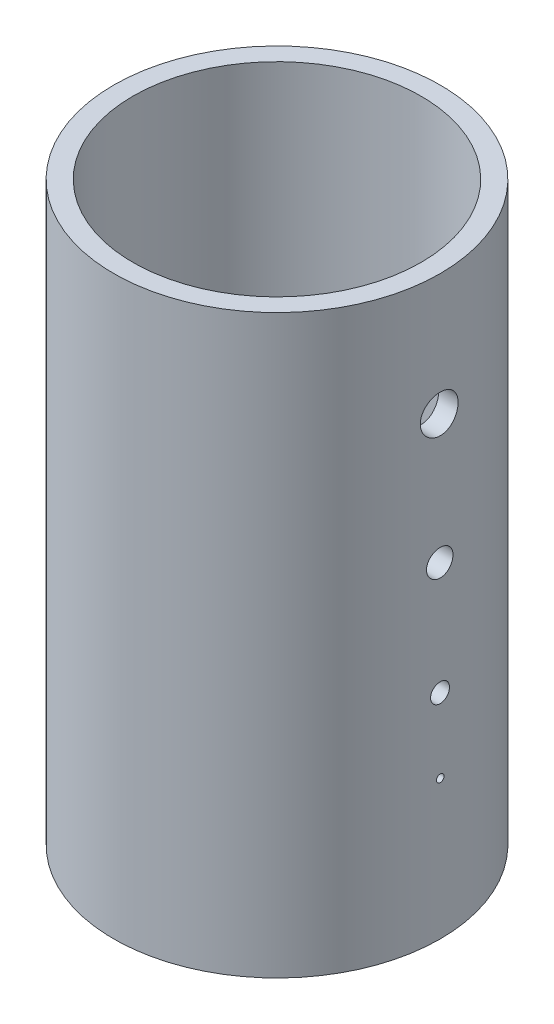
SolidWorks part; units mm, degrees
ref_plane "Front Plane" through (0, 0, 0) normal (0, 0, 1) x (1, 0, 0)
ref_plane "Top Plane" through (0, 0, 0) normal (0, 1, 0) x (1, 0, 0)
ref_plane "Right Plane" through (0, 0, 0) normal (1, 0, 0) x (0, 0, -1)
sketch "Sketch1" plane through (0, 0, 0) normal (0, 0, 1) x (1, 0, 0)
  line L0 (0, 0) -> (-43.18, 0)
  line L1 (-43.18, 0) -> (-43.18, 152.4)
  line L3 (-38.1, 152.4) -> (-38.1, 34.925)
  line L4 (-12.7, 9.525) -> (0, 9.525)
  line L5 (0, 9.525) -> (0, 0)
  line L11 (-43.18, 152.4) -> (-38.1, 152.4)
  arc A0 (-38.1, 34.925) -> (-12.7, 9.525) centre (-12.7, 34.925) ccw
  point P9 (-38.1, 9.525)
  dimension "D3" = 25.4
  dimension "D1" = 38.1
  dimension "D2" = 152.4
  dimension "D4" = 5.08
  dimension "D5" = 9.525
revolve "Revolve1" add sketch "Sketch1" angle 360 about L5
sketch "Sketch2" [suppressed] plane through (0, 0, 0) normal (0, -1, 0) x (1, 0, 0)
  circle A0 centre (0, 0) radius 12.7 construction
  circle A1 centre (0, 12.7) radius 2.032
  point P3 (0, 12.7)
  point P7 (8.9803, 8.9803)
  point P8 (12.7, 0)
  point P9 (8.9803, -8.9803)
  point P10 (0, -12.7)
  point P11 (-8.9803, -8.9803)
  point P12 (-12.7, 0)
  point P13 (-8.9803, 8.9803)
  point P14 (0, 0)
  dimension "D1" = 25.4
  dimension "D3" = 4.064
  dimension "D2" = 8
extrude "Cut-Extrude1" [suppressed] cut sketch "Sketch2" against normal up to next draft 4.35 contours A1
pattern_circular "CirPattern1" [suppressed] count 4 over 360 of bodies 102
fillet "Fillet1" [suppressed] radius 0.3969
chamfer "Chamfer1" [suppressed] distance 0.3969 angle 45
ref_plane "Plane1" through (43.18, 0, 0) normal (1, 0, 0) x (0, 0, -1)
sketch "Sketch3" plane through (43.18, 0, 0) normal (1, 0, 0) x (0, 0, -1)
  line L0 (-43.18, 0) -> (43.18, 0) construction
  line L1 (43.18, 152.4) -> (-43.18, 152.4) construction
  line L2 (-43.18, 0) -> (43.18, 0) construction
  line L3 (43.18, 152.4) -> (-43.18, 152.4) construction
  line L4 (0, 0) -> (0, 152.4) construction
  circle A0 centre (0, 36.8078) radius 1
  circle A1 centre (0, 56.4155) radius 2.5
  circle A2 centre (0, 86.1841) radius 3.5
  circle A3 centre (0, 120.2598) radius 5
  point P14 (0, 0)
  point P15 (0, 0)
  point P16 (0, 0)
  point P17 (0, 36.8078)
  point P18 (0, 68.0057)
  point P19 (0, 56.4155)
  point P20 (0, 86.1841)
  point P21 (0, 120.2598)
  dimension "D1" = 2
  dimension "D2" = 5
  dimension "D3" = 7
  dimension "D4" = 10
extrude "Cut-Extrude2" cut sketch "Sketch3" against normal up to next
